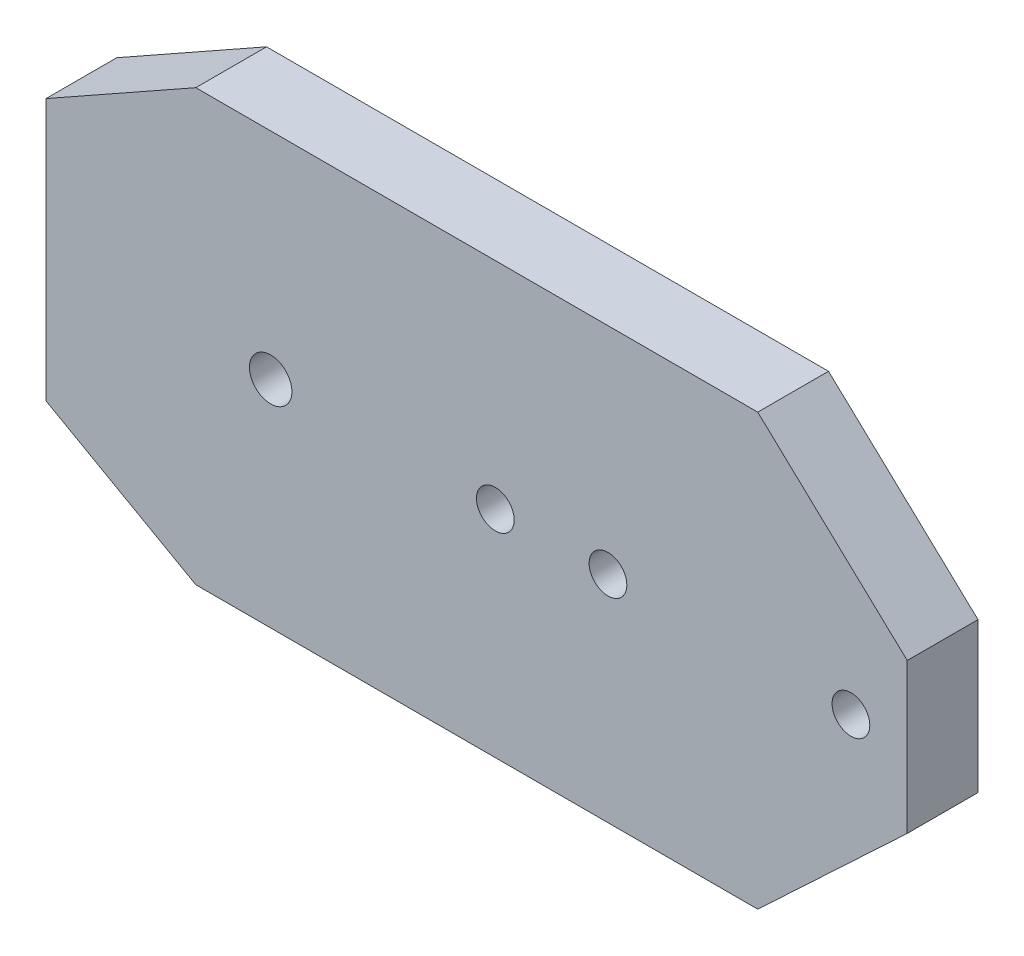
SolidWorks part; units mm, degrees
ref_plane "Front Plane" through (0, 0, 0) normal (0, 0, 1) x (1, 0, 0)
ref_plane "Top Plane" through (0, 0, 0) normal (0, 1, 0) x (1, 0, 0)
ref_plane "Right Plane" through (0, 0, 0) normal (1, 0, 0) x (0, 0, -1)
sketch "Sketch1" plane through (0, 0, 0) normal (0, 0, 1) x (1, 0, 0)
  line L0 (-19.05, -11.1) -> (-6.35, -18.25)
  line L1 (-6.35, -18.25) -> (41.3, -18.25)
  line L2 (41.3, -18.25) -> (53.975, -6.35)
  line L3 (53.975, -6.35) -> (53.975, 6.35)
  line L4 (53.975, 6.35) -> (41.3, 18.25)
  line L5 (41.3, 18.25) -> (-6.35, 18.25)
  line L6 (-6.35, 18.25) -> (-19.05, 11.1)
  line L7 (-19.05, 11.1) -> (-19.05, -11.1)
  circle A0 centre (19.05, 0) radius 1.6
  circle A1 centre (28.6, 0) radius 1.6
  circle A2 centre (49.2, 0) radius 1.6
  circle A3 centre (0, 0) radius 1.8
extrude "Boss-Extrude1" add sketch "Sketch1" along normal blind 6
ref_axis "Pivot" through (0, 0, 6.3) along (0, 0, -1)
ref_plane "LinkPin_px" through (19.05, 0, 0) normal (1, 0, 0) x (0, 0, -1)
ref_axis "LinkPin" through (19.05, 0, 6.3) along (0, 0, -1)
